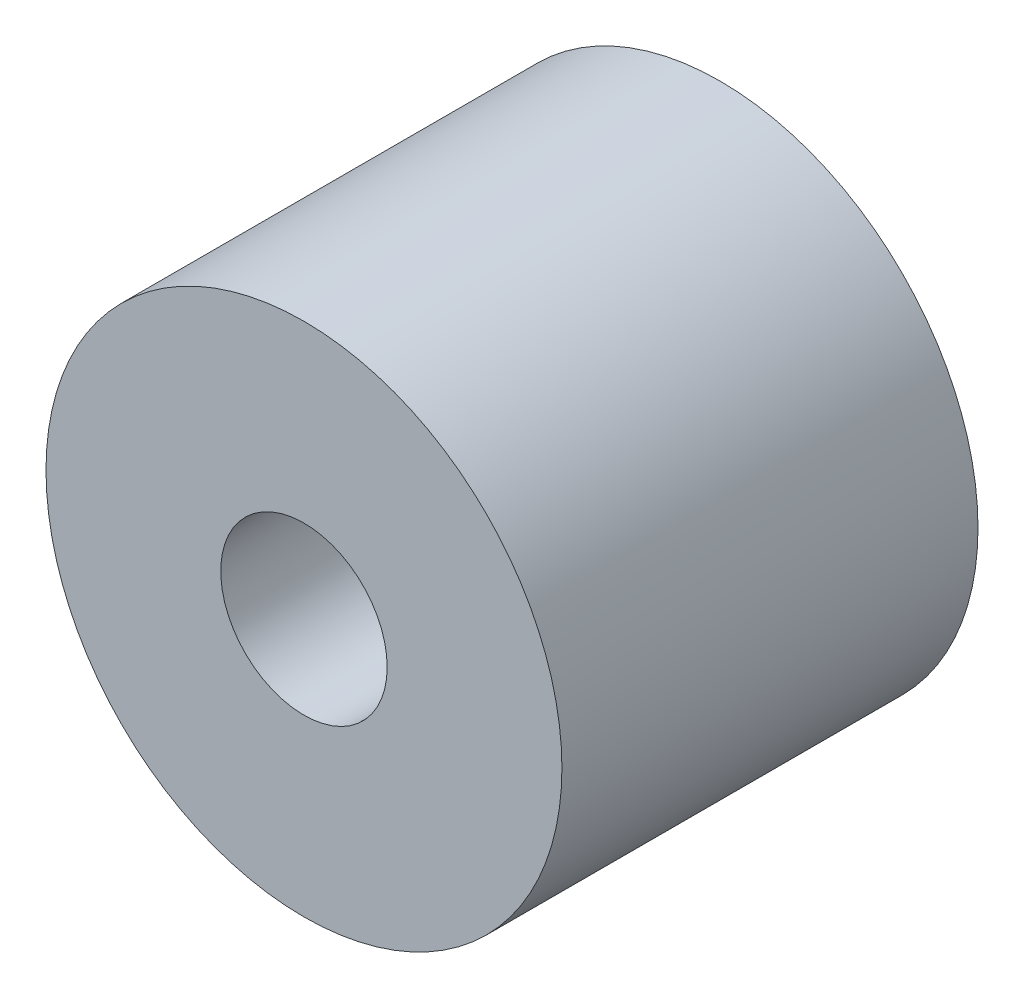
SolidWorks part; units mm, degrees
ref_plane "Front Plane" through (0, 0, 0) normal (0, 0, 1) x (1, 0, 0)
ref_plane "Top Plane" through (0, 0, 0) normal (0, 1, 0) x (1, 0, 0)
ref_plane "Right Plane" through (0, 0, 0) normal (1, 0, 0) x (0, 0, -1)
sketch "Sketch1" plane through (0, 0, 0) normal (0, 0, 1) x (1, 0, 0)
  circle A0 centre (0, 0) radius 15.5
  circle A1 centre (0, 0) radius 5
  dimension "D1" = 31
extrude "Boss-Extrude1" add sketch "Sketch1" along normal blind 25
sketch "Sketch2" plane through (0, 0, 0) normal (0, 1, 0) x (1, 0, 0)
  line L0 (0, 0) -> (0, -25) construction
  line L1 (-15.5, -25) -> (15.5, -25) construction
